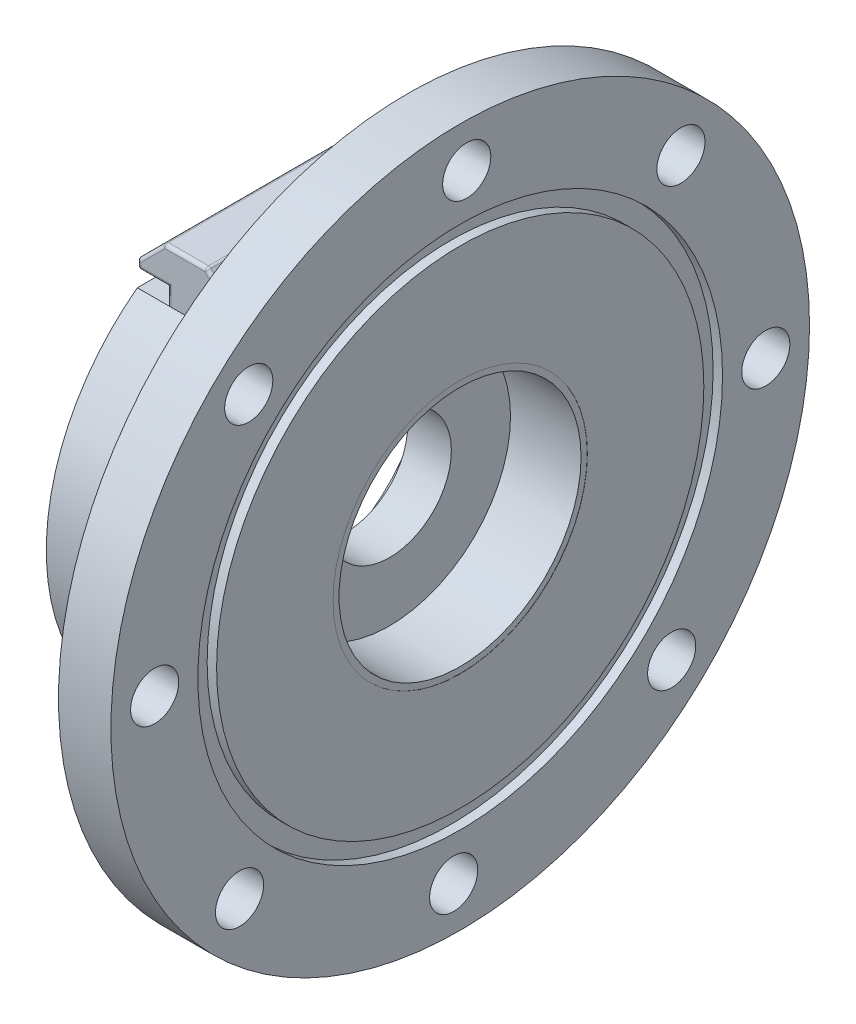
SolidWorks part; units mm, degrees
ref_plane "Front Plane" through (0, 0, 0) normal (0, 0, 1) x (1, 0, 0)
ref_plane "Top Plane" through (0, 0, 0) normal (0, 1, 0) x (1, 0, 0)
ref_plane "Right Plane" through (0, 0, 0) normal (1, 0, 0) x (0, 0, -1)
sketch "Main sketch" plane through (0, 0, 0) normal (0, 0, 1) x (1, 0, 0)
  line L0 (0, 9) -> (0, 20.005)
  line L1 (0, 20.005) -> (-8, 20.005)
  line L2 (-8, 20.005) -> (-8, 23.815)
  line L3 (-8, 33.02) -> (9.017, 33.02)
  line L4 (9.017, 33.02) -> (9.017, 50.8)
  line L5 (9.017, 50.8) -> (16.637, 50.8)
  line L6 (16.637, 50.8) -> (16.637, 38.1508)
  line L7 (16.637, 38.1508) -> (15.2654, 38.1508)
  line L8 (15.2654, 38.1508) -> (15.2654, 35.433)
  line L9 (15.2654, 35.433) -> (16.637, 35.433)
  line L10 (16.637, 35.433) -> (16.637, 18.4912)
  line L11 (16.637, 18.4912) -> (16.6116, 18.4912)
  line L12 (16.6116, 18.4912) -> (16.6116, 17.6022)
  line L13 (16.6116, 17.6022) -> (6.35, 17.6022)
  line L14 (6.35, 17.6022) -> (6.35, 9)
  line L15 (6.35, 9) -> (0, 9)
  line L16 (0, 0) -> (0, 9) construction
  line L17 (-8, 23.815) -> (-10.54, 23.815)
  line L18 (-10.54, 23.815) -> (-10.54, 33.02)
  line L19 (-10.54, 33.02) -> (-8, 33.02)
  point P20 (15.9512, 35.433)
  dimension "D1" = 9
  dimension "D2" = 20.005
  dimension "D4" = 17.6022
  dimension "D5" = 8
  dimension "D6" = 50.8
  dimension "D7" = 18.4912
  dimension "D11" = 6.35
  dimension "D12" = 10.2616
  dimension "D13" = 33.02
  dimension "D14" = 7.62
  dimension "D10" = 1.3716
  dimension "D15" = 2.54
  dimension "D16" = 3.81
  dimension "D3" = 180
  dimension "D17" = 0.0254
  dimension "D18" = 0.0254
  dimension "D8" = 38.1508
  dimension "D9" = 2.7178
ref_axis "Axis1" through (71.9501, 0, 0) along (-1, 0, 0)
revolve "Revolve1" add sketch "Main sketch" angle 360 about axis through (71.9501, 0, 0) along (-1, 0, 0)
sketch "Sketch2" plane through (16.637, 0, 0) normal (1, 0, 0) x (0, 0, -1)
  circle A0 centre (0, 0) radius 44.45 construction
  point P0 (0, 0)
  point P3 (-44.4399, 0.9486)
  point P4 (-32.0945, -30.753)
  point P7 (-0.9486, -44.4399)
  point P8 (30.753, -32.0945)
  point P9 (44.4399, -0.9486)
  point P10 (32.0945, 30.753)
  point P11 (0.9486, 44.4399)
  point P12 (-30.753, 32.0945)
  point P13 (0, 0)
  point P16 (0, 0)
  dimension "D2" = 88.9
  dimension "D1" = 8
hole_wizard "M6 Clearance Hole1" positions "Sketch2" profile "Sketch3" hole size "M6" standard "ISO" end condition through all
sketch "Sketch3" plane through (16.637, 0, 0) normal (0, 1, 0) x (0, 0, -1)
  line L0 (0, 0) -> (0, 27.177)
  line L1 (0, 27.177) -> (3.5, 27.177)
  line L2 (3.5, 27.177) -> (3.5, 0)
  line L5 (3.5, 0) -> (0, 0)
  line L11 (0, -6.35) -> (0, 107.95) construction
  dimension "Thru Hole Dia." = 7
  dimension "Thru Hole Depth" = 27.177
ref_plane "Plane1" through (0, 0, 33.02) normal (0, 0, 1) x (1, 0, 0)
ref_plane "Plane2" through (0, 33.02, 0) normal (0, 1, 0) x (1, 0, 0)
ref_plane "Plane3" through (0, 0, -33.02) normal (0, 0, -1) x (-1, 0, 0)
sketch "Sketch4" plane through (0, 33.02, 0) normal (0, 1, 0) x (1, 0, 0)
  line L0 (-10.54, -33.02) -> (9.017, -33.02) construction
  line L1 (9.017, 33.02) -> (9.017, -33.02) construction
  line L2 (9.017, 33.02) -> (-10.54, 33.02) construction
  line L4 (-10.54, -33.02) -> (9.017, -33.02)
  line L5 (9.017, 33.02) -> (9.017, -33.02)
  line L6 (9.017, 33.02) -> (-10.54, 33.02)
  line L8 (-10.54, 33.02) -> (-10.54, -33.02) construction
  line L9 (-10.54, 33.02) -> (-10.54, -33.02)
extrude "Cut-Extrude1" cut sketch "Sketch4" against normal blind 6.5786
ref_plane "Plane4" through (0, 0, -19.7781) normal (0, 0, 1) x (1, 0, 0)
ref_plane "Plane5" through (0, 0, 19.7781) normal (0, 0, -1) x (-1, 0, 0)
sketch "Sketch5" plane through (0, 0, 19.7781) normal (0, 0, -1) x (-1, 0, 0)
  line L0 (10.54, 26.4414) -> (-9.017, 26.4414) construction
  line L1 (10.54, 26.4414) -> (-9.017, 26.4414)
  line L2 (1.0658, 26.4414) -> (1.0658, 28.8036)
  line L3 (1.0658, 28.8036) -> (-3.3284, 28.8036)
  line L4 (-3.3284, 28.8036) -> (-3.3284, 30.0736)
  line L5 (-3.3284, 30.0736) -> (0.4816, 33.8836)
  line L6 (0.4816, 33.8836) -> (6.73, 33.8836)
  line L7 (3.6058, 33.8836) -> (3.6058, 26.4414) construction
  line L8 (6.1458, 26.4414) -> (1.0658, 26.4414)
  line L9 (6.1458, 26.4414) -> (6.1458, 28.8036)
  line L10 (6.1458, 28.8036) -> (10.54, 28.8036)
  line L11 (10.54, 28.8036) -> (10.54, 30.0736)
  line L12 (10.54, 30.0736) -> (6.73, 33.8836)
  line L14 (10.54, -33.02) -> (10.54, 26.4414) construction
  dimension "D1" = 2.54
  dimension "D2" = 2.3622
  dimension "D3" = 135
  dimension "D4" = 5.08
  dimension "D5" = 6.9342
  dimension "D6" = 1.27
extrude "Boss-Extrude1" add sketch "Sketch5" along normal up to surface (39.5562 mm away) contours L7 L6 L5 L4 L3 L2 L8 | L6 L7 L1 L9 L10 L11 L12 region at (-6.2153, 30.4149, 19.7781) region at (-0.9963, 30.4149, 19.7781) up to plane "Plane4"
fillet "Fillet1" radius 0.508 24 edges at (-3.6058, 33.8836, -19.7781) (-1.0658, 27.6225, 19.7781) (3.3284, 29.4386, 19.7781) (1.1313, 28.8036, 19.7781) (1.4234, 31.9786, 19.7781) (-3.6058, 33.8836, 19.7781) (-8.3429, 28.8036, 19.7781) (-6.1458, 27.6225, 19.7781) (-1.0658, 27.6225, -19.7781) (-6.1458, 27.6225, -19.7781) (-8.3429, 28.8036, -19.7781) (-8.635, 31.9786, -19.7781) (-6.73, 33.8836, 0) (-8.635, 31.9786, 19.7781) (-10.54, 29.4386, 19.7781) (-10.54, 30.0736, 0) (-10.54, 28.8036, 0) (-10.54, 29.4386, -19.7781) (1.4234, 31.9786, -19.7781) (3.3284, 29.4386, -19.7781) (1.1313, 28.8036, -19.7781) (-0.4816, 33.8836, 0) (3.3284, 30.0736, 0) (3.3284, 28.8036, 0)
mirror "Mirror1" about plane through (0, 0, 0) normal (0, 1, 0) of "Fillet1", "Boss-Extrude1", "Cut-Extrude1"
equation "\"Shaft_OD\"= 17mm'outer diameter of shaft"
equation "\"O_Ring_ID\"= 2.864in"
equation "\"O_Ring_CS\"= .070in'cross section"
equation "\"Bearing_OD\"= 40.01mm"
equation "\"Bearing_Depth\"= 8mm'depth bearing goes into the casing"
equation "\"Stationary_Face_Seal_OD\"= 1.386in"
equation "\"Flange_Dia\"= 4in"
equation "\"Screw_Dia\"= 6mm"
equation "\"Seal_Space\"= .3in"
equation "\"D1@Main sketch\"=\"Shaft_OD\" / 2 + .5mm"
equation "\"D2@Main sketch\" = \"Bearing_OD\" / 2"
equation "\"D4@Main sketch\" = \"Stationary_Face_Seal_OD\" / 2"
equation "\"D5@Main sketch\" = \"Bearing_Depth\""
equation "\"D6@Main sketch\" = \"Flange_Dia\" / 2"
equation "\"Seal_Area_Dia\"= 37mm"
equation "\"D7@Main sketch\"=\"Seal_space_Dia\"/2"
equation "\"Face_Seal_Height\"= 0.404in"
equation "\"D12@Main sketch\" = \"Face_Seal_Height\""
equation "\"Housing_OR\"= 1.3in'Outer radius of housing"
equation "\"D10@Main sketch\"=.054"
equation "\"D2@Sketch2\"=\"Flange_Dia\"-\"Screw_offset\""
equation "\"Screw_offset\"= .5in'offset of screws from flange OD."
equation "\"Seal_space_Dia\"= \"Stationary_Face_Seal_OD\" + .07'diameter of the space for the face seal"
equation "\"D8@Main sketch\"=(\"O_Ring_ID\"+2*\"O_Ring_CS\")/2"
equation "\"Groove_width\"=0.107"
equation "\"D9@Main sketch\"=\"Groove_width\""
